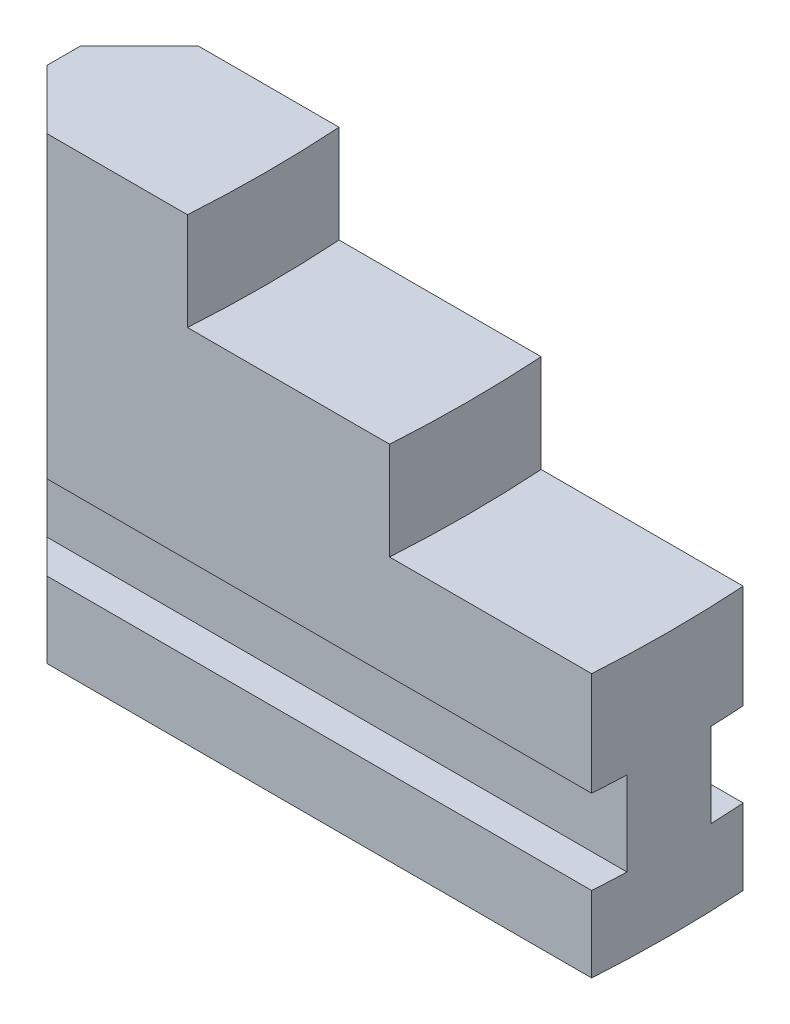
SolidWorks part; units mm, degrees
material "Plain Carbon Steel"
ref_plane "Front Plane" through (0, 0, 0) normal (0, 0, 1) x (1, 0, 0)
ref_plane "Top Plane" through (0, 0, 0) normal (0, 1, 0) x (1, 0, 0)
ref_plane "Right Plane" through (0, 0, 0) normal (1, 0, 0) x (0, 0, -1)
sketch "Sketch1" plane through (0, 0, 0) normal (0, 0, 1) x (1, 0, 0)
  line L0 (0, 0) -> (0, 54.5)
  line L1 (0, 54.5) -> (24, 54.5)
  line L2 (24, 54.5) -> (24, 42.9)
  line L3 (24, 42.9) -> (48, 42.9)
  line L4 (48, 42.9) -> (48, 31.3)
  line L5 (48, 31.3) -> (72, 31.3)
  line L6 (72, 31.3) -> (72, 0)
  line L7 (72, 0) -> (0, 0)
  dimension "D1" = 54.5
  dimension "D2" = 24
  dimension "D3" = 11.6
  dimension "D4" = 11.6
  dimension "D5" = 24
  dimension "D6" = 24
extrude "Boss-Extrude1" add sketch "Sketch1" along normal mid plane 18
sketch "Sketch3" plane through (0, 0, 0) normal (-1, 0, 0) x (0, 0, 1)
  line L0 (-9, 54.5) -> (-9, 0) construction
  line L1 (-9, 19) -> (-5, 19)
  line L2 (-9, 19) -> (-9, 9)
  line L3 (-9, 9) -> (-5, 9)
  line L4 (-5, 19) -> (-5, 9)
  line L5 (9, 0) -> (-9, 0) construction
  line L6 (0, 0) -> (0, 54.5) construction
  line L7 (9, 54.5) -> (-9, 54.5) construction
  line L8 (5, 19) -> (5, 9)
  line L9 (9, 9) -> (5, 9)
  line L10 (9, 19) -> (9, 9)
  line L11 (9, 19) -> (5, 19)
  dimension "D1" = 4
  dimension "D2" = 10
  dimension "D3" = 9
extrude "Cut-Extrude2" cut sketch "Sketch3" against normal through all
sketch "Sketch4" plane through (0, 42.9, 0) normal (0, 1, 0) x (1, 0, 0)
  line L0 (48, 9) -> (24, 9) construction
  line L1 (48, -9) -> (24, -9) construction
  line L2 (49.7104, -9) -> (47.7104, -9)
  line L3 (23.7104, 9) -> (25.7104, 9)
  line L4 (72, 9) -> (48, 9) construction
  line L5 (25.7104, 9) -> (25.7104, -9)
  line L6 (72, -9) -> (48, -9) construction
  line L7 (25.7104, -9) -> (23.7104, -9)
  line L8 (-116, 0) -> (48, 0) construction
  line L9 (48, -9) -> (48, 9) construction
  line L10 (36, 9) -> (36, -9) construction
  line L11 (24, -9) -> (0, -9) construction
  line L12 (24, -9) -> (24, 9) construction
  line L13 (47.7104, 9) -> (49.7104, 9)
  line L14 (49.7104, 9) -> (49.7104, -9)
  line L15 (73.7104, -9) -> (71.7104, -9)
  line L16 (71.7104, 9) -> (73.7104, 9)
  line L17 (73.7104, 9) -> (73.7104, -9)
  arc A0 (23.7104, 9) -> (23.7104, -9) centre (-116, 0) cw
  arc A1 (47.7104, 9) -> (47.7104, -9) centre (-92, 0) cw
  arc A2 (71.7104, 9) -> (71.7104, -9) centre (-68, 0) cw
  dimension "D1" = 140
  dimension "D2" = 2
  dimension "D3" = 3
extrude "Cut-Extrude3" cut sketch "Sketch4" along direction (0, -1, 0) on the side against the normal up to surface from surface up to face at (36, 42.9, 0) starting at face at (12, 54.5, 0)
extrude "Cut-Extrude7" cut sketch "Sketch4<3>" along direction (0, -1, 0) on the side against the normal up to surface (11.6 mm away) from surface contours L2 A1 L13 L14 up to face at (60, 31.3, 0) starting at face at (35.9276, 42.9, 0)
sketch "Sketch4<3>" plane through (0, 42.9, 0) normal (0, 1, 0) x (1, 0, 0) same geometry as "Sketch4"
extrude "Cut-Extrude8" cut sketch "Sketch4<4>" against normal up to surface (42.9 mm away) from surface contours L15 A2 L16 L17 up to face at (36, 0, 0) starting at face at (59.9276, 31.3, 0)
sketch "Sketch4<4>" plane through (0, 42.9, 0) normal (0, 1, 0) x (1, 0, 0) same geometry as "Sketch4"
chamfer "Chamfer1" distance 7 angle 45 2 edges at (0, 36.75, -9) (0, 36.75, 9)
